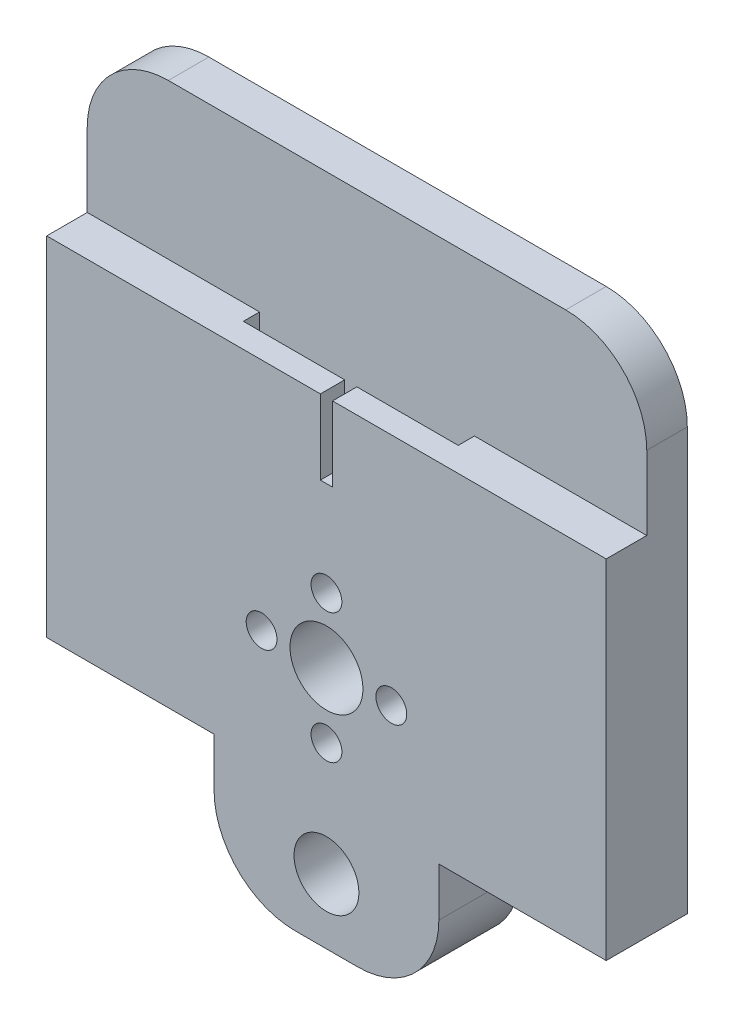
SolidWorks part; units mm, degrees
ref_plane "Front Plane" through (0, 0, 0) normal (0, 0, 1) x (1, 0, 0)
ref_plane "Top Plane" through (0, 0, 0) normal (0, 1, 0) x (1, 0, 0)
ref_plane "Right Plane" through (0, 0, 0) normal (1, 0, 0) x (0, 0, -1)
sketch "Sketch1" plane through (0, 0, 0) normal (0, 0, 1) x (1, 0, 0)
  line L0 (0, 39) -> (0, -39) construction
  line L1 (-34.5, 39) -> (34.5, 39)
  line L2 (34.5, 39) -> (34.5, -23)
  line L3 (34.5, -23) -> (13.8611, -23)
  line L4 (13.8611, -23) -> (13.8611, -39)
  line L5 (13.8611, -39) -> (-13.8611, -39)
  line L6 (-13.8611, -23) -> (-13.8611, -39)
  line L7 (-34.5, -23) -> (-13.8611, -23)
  line L8 (-34.5, 39) -> (-34.5, -23)
  dimension "D1" = 69
  dimension "D2" = 27.7222
  dimension "D3" = 16
  dimension "D4" = 62
extrude "Boss-Extrude1" add sketch "Sketch1" along normal blind 10
sketch "Sketch2" plane through (0, 0, 10) normal (0, 0, 1) x (1, 0, 0)
  line L0 (0, 39) -> (0, -39) construction
  line L1 (34.5, 39) -> (-34.5, 39) construction
  line L2 (-13.8611, -39) -> (13.8611, -39) construction
  line L3 (-13.8611, -31) -> (13.8611, -31) construction
  line L4 (-13.8611, -23) -> (-13.8611, -39) construction
  line L5 (13.8611, -39) -> (13.8611, -23) construction
  line L7 (-34.5, 39) -> (-34.5, -23) construction
  line L8 (34.5, -23) -> (34.5, 39) construction
  line L9 (-34.5, 32.3714) -> (34.5, 32.3714) construction
  circle A0 centre (0, -31) radius 4
  circle A1 centre (0, -9) radius 4.5
  circle A2 centre (0, -1) radius 1.9
  circle A6 centre (8, -9) radius 1.9
  circle A7 centre (0, -17) radius 1.9
  circle A8 centre (-8, -9) radius 1.9
  point P33 (2.405, -11.405)
  point P34 (0, -9)
  dimension "D1" = 9
  dimension "D2" = 8
  dimension "D3" = 22
  dimension "D4" = 3.8
  dimension "D5" = 8
  dimension "D6" = 4
extrude "Cut-Extrude1" cut sketch "Sketch2" against normal through all
sketch "Sketch4" plane through (-34.5, 0, 0) normal (-1, 0, 0) x (0, 0, 1)
  line L0 (5, 39) -> (5, 19.9)
  line L1 (10, 39) -> (0, 39) construction
  line L2 (5, 19.9) -> (10, 19.9)
  line L3 (10, 39) -> (10, -23) construction
  dimension "D1" = 19.1
extrude "Cut-Extrude2" cut sketch "Sketch4" against normal through all and the other way through all
sketch "Sketch5" plane through (0, 0, 10) normal (0, 0, 1) x (1, 0, 0)
  line L0 (0, 19.9) -> (0, -4.5) construction
  line L1 (-34.5, 19.9) -> (34.5, 19.9) construction
  line L2 (-0.75, 19.9) -> (-0.75, 10.6925)
  line L3 (-34.5, 19.9) -> (34.5, 19.9) construction
  line L4 (-0.75, 10.6925) -> (0.75, 10.6925)
  line L5 (-0.75, 19.9) -> (0.75, 19.9)
  line L6 (0.75, 19.9) -> (0.75, 10.6925)
  circle A0 centre (0, -9) radius 4.5 construction
  point P13 (0, 10.6925)
  dimension "D1" = 9.2075
  dimension "D2" = 0.75
extrude "Cut-Extrude4" cut sketch "Sketch5" against normal blind 5
sketch "Sketch6" plane through (0, 19.9, 0) normal (0, 1, 0) x (1, 0, 0)
  line L0 (-13.25, -5) -> (-13.25, -7)
  line L1 (-34.5, -5) -> (-0.75, -5) construction
  line L2 (-13.25, -7) -> (-0.75, -7)
  line L3 (-0.75, -5) -> (-0.75, -10) construction
  line L4 (-13.25, -5) -> (-0.75, -5)
  line L5 (-0.75, -5) -> (-0.75, -7)
  dimension "D1" = 12.5
  dimension "D2" = 2
extrude "Cut-Extrude5" cut sketch "Sketch6" against normal blind 9.954
sketch "Sketch7" plane through (0, 19.9, 0) normal (0, 1, 0) x (1, 0, 0)
  line L0 (13.25, -5) -> (13.25, -7)
  line L1 (0.75, -5) -> (34.5, -5) construction
  line L2 (13.25, -7) -> (0.75, -7)
  line L3 (0.75, -5) -> (0.75, -10) construction
  line L4 (0.75, -7) -> (0.75, -5)
  line L5 (0.75, -5) -> (13.25, -5)
  dimension "D1" = 12.5
  dimension "D2" = 2
extrude "Cut-Extrude6" cut sketch "Sketch7" against normal blind 9.954
fillet "Fillet2" radius 10 2 edges at (13.8611, -39, 5) (-13.8611, -39, 5)
fillet "Fillet3" radius 10 2 edges at (-34.5, 39, 2.5) (34.5, 39, 2.5)
sketch "Sketch8" plane through (0, -23, 0) normal (0, -1, 0) x (1, 0, 0)
  line L0 (-34.5, 0) -> (-13.8611, 0) construction
  line L1 (-34.5, 10) -> (-34.5, 0) construction
  circle A0 centre (-29.2517, 3) radius 1.25
  circle A1 centre (-19.2517, 3) radius 1.25
  dimension "D1" = 3
  dimension "D2" = 10
  dimension "D3" = 5.2483
  dimension "D4" = 2.5
  dimension "D5" = 3
extrude "Cut-Extrude7" cut sketch "Sketch8" against normal blind 16
ref_plane "Plane1" through (0, 0, 0) normal (-1, 0, 0) x (0, 0, 1)
mirror "Mirror1" about plane through (0, 0, 0) normal (-1, 0, 0) of "Cut-Extrude7"
